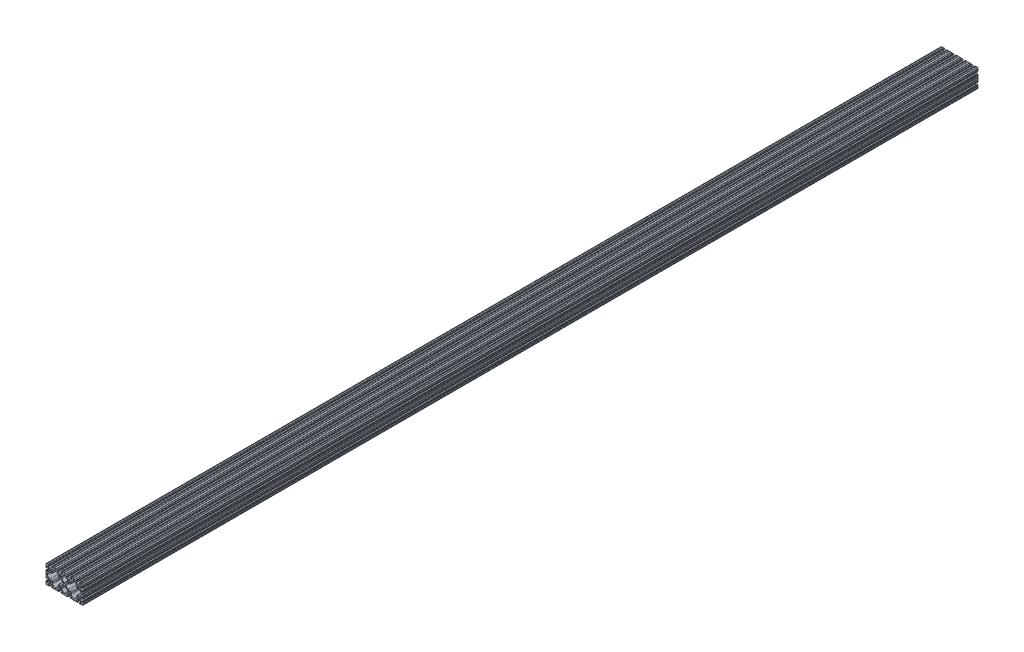
SolidWorks part; units mm, degrees
material "6105-T5 Aluminum"
ref_plane "Front Plane" through (0, 0, 0) normal (0, 0, 1) x (1, 0, 0)
ref_plane "Top Plane" through (0, 0, 0) normal (0, 1, 0) x (1, 0, 0)
ref_plane "Right Plane" through (0, 0, 0) normal (1, 0, 0) x (0, 0, -1)
sketch "Sketch1" plane through (0, 0, 0) normal (0, 0, 1) x (1, 0, 0)
  line L0 (-2.0655, -33.1609) -> (-10.9208, -24.3055)
  line L1 (-12.312, -20.9469) -> (-12.312, -17.1531)
  line L2 (-10.9208, -13.7945) -> (-2.0655, -4.9391)
  line L3 (2.0655, -4.9391) -> (10.9208, -13.7945)
  line L4 (12.312, -17.1531) -> (12.312, -20.9469)
  line L5 (10.9208, -24.3055) -> (2.0655, -33.1609)
  line L6 (22.613, -12.312) -> (17.1531, -12.312)
  line L7 (13.7945, -10.9208) -> (4.9391, -2.0655)
  line L8 (4.9391, 2.0655) -> (13.7945, 10.9208)
  line L9 (17.1531, 12.312) -> (22.613, 12.312)
  line L10 (25.788, 15.487) -> (25.788, 20.9469)
  line L11 (27.1792, 24.3055) -> (36.0345, 33.1609)
  line L12 (40.1655, 33.1609) -> (49.0208, 24.3055)
  line L13 (50.412, 20.9469) -> (50.412, 15.487)
  line L14 (53.587, 12.312) -> (59.0469, 12.312)
  line L15 (62.4055, 10.9208) -> (71.2609, 2.0655)
  line L16 (71.2609, -2.0655) -> (62.4055, -10.9208)
  line L17 (59.0469, -12.312) -> (53.587, -12.312)
  line L18 (50.412, -15.487) -> (50.412, -20.9469)
  line L19 (49.0208, -24.3055) -> (40.1655, -33.1609)
  line L20 (36.0345, -33.1609) -> (27.1792, -24.3055)
  line L21 (25.788, -20.9469) -> (25.788, -15.487)
  line L22 (2.0655, 33.1609) -> (10.9208, 24.3055)
  line L23 (12.312, 20.9469) -> (12.312, 17.1531)
  line L24 (10.9208, 13.7945) -> (2.0655, 4.9391)
  line L25 (-2.0655, 4.9391) -> (-10.9208, 13.7945)
  line L26 (-12.312, 17.1531) -> (-12.312, 20.9469)
  line L27 (-10.9208, 24.3055) -> (-2.0655, 33.1609)
  line L28 (-53.587, -12.312) -> (-59.0469, -12.312)
  line L29 (-62.4055, -10.9208) -> (-71.2609, -2.0655)
  line L30 (-71.2609, 2.0655) -> (-62.4055, 10.9208)
  line L31 (-59.0469, 12.312) -> (-53.587, 12.312)
  line L32 (-50.412, 15.487) -> (-50.412, 20.9469)
  line L33 (-49.0208, 24.3055) -> (-40.1655, 33.1609)
  line L34 (-36.0345, 33.1609) -> (-27.1792, 24.3055)
  line L35 (-25.788, 20.9469) -> (-25.788, 15.487)
  line L36 (-22.613, 12.312) -> (-17.1531, 12.312)
  line L37 (-13.7945, 10.9208) -> (-4.9391, 2.0655)
  line L38 (-4.9391, -2.0655) -> (-13.7945, -10.9208)
  line L39 (-17.1531, -12.312) -> (-22.613, -12.312)
  line L40 (-25.788, -15.487) -> (-25.788, -20.9469)
  line L41 (-27.1792, -24.3055) -> (-36.0345, -33.1609)
  line L42 (-40.1655, -33.1609) -> (-49.0208, -24.3055)
  line L43 (-50.412, -20.9469) -> (-50.412, -15.487)
  line L44 (-3.2004, -38.1) -> (3.2004, -38.1)
  line L45 (4.7244, -38.1) -> (9.5504, -38.1)
  line L46 (11.0744, -38.1) -> (13.4112, -38.1)
  line L47 (14.986, -36.5252) -> (14.986, -35.6108)
  line L48 (13.4112, -34.036) -> (9.652, -34.036)
  line L49 (8.763, -33.147) -> (8.763, -32.5789)
  line L50 (9.0234, -31.9503) -> (13.7945, -27.1792)
  line L51 (17.1531, -25.788) -> (20.9469, -25.788)
  line L52 (24.3055, -27.1792) -> (29.0766, -31.9503)
  line L53 (29.337, -32.5789) -> (29.337, -33.147)
  line L54 (28.448, -34.036) -> (24.6888, -34.036)
  line L55 (23.114, -35.6108) -> (23.114, -36.5252)
  line L56 (24.6888, -38.1) -> (27.0256, -38.1)
  line L57 (28.5496, -38.1) -> (33.3756, -38.1)
  line L58 (34.8996, -38.1) -> (41.3004, -38.1)
  line L59 (42.8244, -38.1) -> (47.6504, -38.1)
  line L60 (49.1744, -38.1) -> (51.5112, -38.1)
  line L61 (53.086, -36.5252) -> (53.086, -35.6108)
  line L62 (51.5112, -34.036) -> (47.752, -34.036)
  line L63 (46.863, -33.147) -> (46.863, -32.5789)
  line L64 (47.1234, -31.9503) -> (51.8945, -27.1792)
  line L65 (55.2531, -25.788) -> (59.0469, -25.788)
  line L66 (62.4055, -27.1792) -> (67.1766, -31.9503)
  line L67 (67.437, -32.5789) -> (67.437, -33.147)
  line L68 (66.548, -34.036) -> (62.7888, -34.036)
  line L69 (61.214, -35.6108) -> (61.214, -36.5252)
  line L70 (62.7888, -38.1) -> (65.1256, -38.1)
  line L71 (66.6496, -38.1) -> (71.4756, -38.1)
  line L72 (72.9996, -38.1) -> (73.025, -38.1)
  line L73 (76.2, -34.925) -> (76.2, -34.8996)
  line L74 (76.2, -33.3756) -> (76.2, -28.5496)
  line L75 (76.2, -27.0256) -> (76.2, -24.6888)
  line L76 (74.6252, -23.114) -> (73.7108, -23.114)
  line L77 (72.136, -24.6888) -> (72.136, -28.448)
  line L78 (71.247, -29.337) -> (70.6789, -29.337)
  line L79 (70.0503, -29.0766) -> (65.2792, -24.3055)
  line L80 (63.888, -20.9469) -> (63.888, -17.1531)
  line L81 (65.2792, -13.7945) -> (70.0503, -9.0234)
  line L82 (70.6789, -8.763) -> (71.247, -8.763)
  line L83 (72.136, -9.652) -> (72.136, -13.4112)
  line L84 (73.7108, -14.986) -> (74.6252, -14.986)
  line L85 (76.2, -13.4112) -> (76.2, -11.0744)
  line L86 (76.2, -9.5504) -> (76.2, -4.7244)
  line L87 (76.2, -3.2004) -> (76.2, 3.2004)
  line L88 (76.2, 4.7244) -> (76.2, 9.5504)
  line L89 (76.2, 11.0744) -> (76.2, 13.4112)
  line L90 (74.6252, 14.986) -> (73.7108, 14.986)
  line L91 (72.136, 13.4112) -> (72.136, 9.652)
  line L92 (71.247, 8.763) -> (70.6789, 8.763)
  line L93 (70.0503, 9.0234) -> (65.2792, 13.7945)
  line L94 (63.888, 17.1531) -> (63.888, 20.9469)
  line L95 (65.2792, 24.3055) -> (70.0503, 29.0766)
  line L96 (70.6789, 29.337) -> (71.247, 29.337)
  line L97 (72.136, 28.448) -> (72.136, 24.6888)
  line L98 (73.7108, 23.114) -> (74.6252, 23.114)
  line L99 (76.2, 24.6888) -> (76.2, 27.0256)
  line L100 (76.2, 28.5496) -> (76.2, 33.3756)
  line L101 (76.2, 34.8996) -> (76.2, 34.925)
  line L102 (73.025, 38.1) -> (72.9996, 38.1)
  line L103 (71.4756, 38.1) -> (66.6496, 38.1)
  line L104 (65.1256, 38.1) -> (62.7888, 38.1)
  line L105 (61.214, 36.5252) -> (61.214, 35.6108)
  line L106 (62.7888, 34.036) -> (66.548, 34.036)
  line L107 (67.437, 33.147) -> (67.437, 32.5789)
  line L108 (67.1766, 31.9503) -> (62.4055, 27.1792)
  line L109 (59.0469, 25.788) -> (55.2531, 25.788)
  line L110 (51.8945, 27.1792) -> (47.1234, 31.9503)
  line L111 (46.863, 32.5789) -> (46.863, 33.147)
  line L112 (47.752, 34.036) -> (51.5112, 34.036)
  line L113 (53.086, 35.6108) -> (53.086, 36.5252)
  line L114 (51.5112, 38.1) -> (49.1744, 38.1)
  line L115 (47.6504, 38.1) -> (42.8244, 38.1)
  line L116 (41.3004, 38.1) -> (34.8996, 38.1)
  line L117 (33.3756, 38.1) -> (28.5496, 38.1)
  line L118 (27.0256, 38.1) -> (24.6888, 38.1)
  line L119 (23.114, 36.5252) -> (23.114, 35.6108)
  line L120 (24.6888, 34.036) -> (28.448, 34.036)
  line L121 (29.337, 33.147) -> (29.337, 32.5789)
  line L122 (29.0766, 31.9503) -> (24.3055, 27.1792)
  line L123 (20.9469, 25.788) -> (17.1531, 25.788)
  line L124 (13.7945, 27.1792) -> (9.0234, 31.9503)
  line L125 (8.763, 32.5789) -> (8.763, 33.147)
  line L126 (9.652, 34.036) -> (13.4112, 34.036)
  line L127 (14.986, 35.6108) -> (14.986, 36.5252)
  line L128 (13.4112, 38.1) -> (11.0744, 38.1)
  line L129 (9.5504, 38.1) -> (4.7244, 38.1)
  line L130 (3.2004, 38.1) -> (-3.2004, 38.1)
  line L131 (-4.7244, 38.1) -> (-9.5504, 38.1)
  line L132 (-11.0744, 38.1) -> (-13.4112, 38.1)
  line L133 (-14.986, 36.5252) -> (-14.986, 35.6108)
  line L134 (-13.4112, 34.036) -> (-9.652, 34.036)
  line L135 (-8.763, 33.147) -> (-8.763, 32.5789)
  line L136 (-9.0234, 31.9503) -> (-13.7945, 27.1792)
  line L137 (-17.1531, 25.788) -> (-20.9469, 25.788)
  line L138 (-24.3055, 27.1792) -> (-29.0766, 31.9503)
  line L139 (-29.337, 32.5789) -> (-29.337, 33.147)
  line L140 (-28.448, 34.036) -> (-24.6888, 34.036)
  line L141 (-23.114, 35.6108) -> (-23.114, 36.5252)
  line L142 (-24.6888, 38.1) -> (-27.0256, 38.1)
  line L143 (-28.5496, 38.1) -> (-33.3756, 38.1)
  line L144 (-34.8996, 38.1) -> (-41.3004, 38.1)
  line L145 (-42.8244, 38.1) -> (-47.6504, 38.1)
  line L146 (-49.1744, 38.1) -> (-51.5112, 38.1)
  line L147 (-53.086, 36.5252) -> (-53.086, 35.6108)
  line L148 (-51.5112, 34.036) -> (-47.752, 34.036)
  line L149 (-46.863, 33.147) -> (-46.863, 32.5789)
  line L150 (-47.1234, 31.9503) -> (-51.8945, 27.1792)
  line L151 (-55.2531, 25.788) -> (-59.0469, 25.788)
  line L152 (-62.4055, 27.1792) -> (-67.1766, 31.9503)
  line L153 (-67.437, 32.5789) -> (-67.437, 33.147)
  line L154 (-66.548, 34.036) -> (-62.7888, 34.036)
  line L155 (-61.214, 35.6108) -> (-61.214, 36.5252)
  line L156 (-62.7888, 38.1) -> (-65.1256, 38.1)
  line L157 (-66.6496, 38.1) -> (-71.4756, 38.1)
  line L158 (-72.9996, 38.1) -> (-73.025, 38.1)
  line L159 (-76.2, 34.925) -> (-76.2, 34.8996)
  line L160 (-76.2, 33.3756) -> (-76.2, 28.5496)
  line L161 (-76.2, 27.0256) -> (-76.2, 24.6888)
  line L162 (-74.6252, 23.114) -> (-73.7108, 23.114)
  line L163 (-72.136, 24.6888) -> (-72.136, 28.448)
  line L164 (-71.247, 29.337) -> (-70.6789, 29.337)
  line L165 (-70.0503, 29.0766) -> (-65.2792, 24.3055)
  line L166 (-63.888, 20.9469) -> (-63.888, 17.1531)
  line L167 (-65.2792, 13.7945) -> (-70.0503, 9.0234)
  line L168 (-70.6789, 8.763) -> (-71.247, 8.763)
  line L169 (-72.136, 9.652) -> (-72.136, 13.4112)
  line L170 (-73.7108, 14.986) -> (-74.6252, 14.986)
  line L171 (-76.2, 13.4112) -> (-76.2, 11.0744)
  line L172 (-76.2, 9.5504) -> (-76.2, 4.7244)
  line L173 (-76.2, 3.2004) -> (-76.2, -3.2004)
  line L174 (-76.2, -4.7244) -> (-76.2, -9.5504)
  line L175 (-76.2, -11.0744) -> (-76.2, -13.4112)
  line L176 (-74.6252, -14.986) -> (-73.7108, -14.986)
  line L177 (-72.136, -13.4112) -> (-72.136, -9.652)
  line L178 (-71.247, -8.763) -> (-70.6789, -8.763)
  line L179 (-70.0503, -9.0234) -> (-65.2792, -13.7945)
  line L180 (-63.888, -17.1531) -> (-63.888, -20.9469)
  line L181 (-65.2792, -24.3055) -> (-70.0503, -29.0766)
  line L182 (-70.6789, -29.337) -> (-71.247, -29.337)
  line L183 (-72.136, -28.448) -> (-72.136, -24.6888)
  line L184 (-73.7108, -23.114) -> (-74.6252, -23.114)
  line L185 (-76.2, -24.6888) -> (-76.2, -27.0256)
  line L186 (-76.2, -28.5496) -> (-76.2, -33.3756)
  line L187 (-76.2, -34.8996) -> (-76.2, -34.925)
  line L188 (-73.025, -38.1) -> (-72.9996, -38.1)
  line L189 (-71.4756, -38.1) -> (-66.6496, -38.1)
  line L190 (-65.1256, -38.1) -> (-62.7888, -38.1)
  line L191 (-61.214, -36.5252) -> (-61.214, -35.6108)
  line L192 (-62.7888, -34.036) -> (-66.548, -34.036)
  line L193 (-67.437, -33.147) -> (-67.437, -32.5789)
  line L194 (-67.1766, -31.9503) -> (-62.4055, -27.1792)
  line L195 (-59.0469, -25.788) -> (-55.2531, -25.788)
  line L196 (-51.8945, -27.1792) -> (-47.1234, -31.9503)
  line L197 (-46.863, -32.5789) -> (-46.863, -33.147)
  line L198 (-47.752, -34.036) -> (-51.5112, -34.036)
  line L199 (-53.086, -35.6108) -> (-53.086, -36.5252)
  line L200 (-51.5112, -38.1) -> (-49.1744, -38.1)
  line L201 (-47.6504, -38.1) -> (-42.8244, -38.1)
  line L202 (-41.3004, -38.1) -> (-34.8996, -38.1)
  line L203 (-33.3756, -38.1) -> (-28.5496, -38.1)
  line L204 (-27.0256, -38.1) -> (-24.6888, -38.1)
  line L205 (-23.114, -36.5252) -> (-23.114, -35.6108)
  line L206 (-24.6888, -34.036) -> (-28.448, -34.036)
  line L207 (-29.337, -33.147) -> (-29.337, -32.5789)
  line L208 (-29.0766, -31.9503) -> (-24.3055, -27.1792)
  line L209 (-20.9469, -25.788) -> (-17.1531, -25.788)
  line L210 (-13.7945, -27.1792) -> (-9.0234, -31.9503)
  line L211 (-8.763, -32.5789) -> (-8.763, -33.147)
  line L212 (-9.652, -34.036) -> (-13.4112, -34.036)
  line L213 (-14.986, -35.6108) -> (-14.986, -36.5252)
  line L214 (-13.4112, -38.1) -> (-11.0744, -38.1)
  line L215 (-9.5504, -38.1) -> (-4.7244, -38.1)
  arc A0 (-2.0655, -33.1609) -> (2.0655, -33.1609) centre (0, -31.0954) ccw
  arc A1 (-12.312, -20.9469) -> (-10.9208, -24.3055) centre (-7.5622, -20.9469) ccw
  arc A2 (-10.9208, -13.7945) -> (-12.312, -17.1531) centre (-7.5622, -17.1531) ccw
  arc A3 (2.0655, -4.9391) -> (-2.0655, -4.9391) centre (0, -7.0046) ccw
  arc A4 (12.312, -17.1531) -> (10.9208, -13.7945) centre (7.5622, -17.1531) ccw
  arc A5 (10.9208, -24.3055) -> (12.312, -20.9469) centre (7.5622, -20.9469) ccw
  arc A6 (25.788, -15.487) -> (22.613, -12.312) centre (22.613, -15.487) ccw
  arc A7 (13.7945, -10.9208) -> (17.1531, -12.312) centre (17.1531, -7.5622) ccw
  arc A8 (4.9391, 2.0655) -> (4.9391, -2.0655) centre (7.0046, 0) ccw
  arc A9 (17.1531, 12.312) -> (13.7945, 10.9208) centre (17.1531, 7.5622) ccw
  arc A10 (22.613, 12.312) -> (25.788, 15.487) centre (22.613, 15.487) ccw
  arc A11 (27.1792, 24.3055) -> (25.788, 20.9469) centre (30.5378, 20.9469) ccw
  arc A12 (40.1655, 33.1609) -> (36.0345, 33.1609) centre (38.1, 31.0954) ccw
  arc A13 (50.412, 20.9469) -> (49.0208, 24.3055) centre (45.6622, 20.9469) ccw
  arc A14 (50.412, 15.487) -> (53.587, 12.312) centre (53.587, 15.487) ccw
  arc A15 (62.4055, 10.9208) -> (59.0469, 12.312) centre (59.0469, 7.5622) ccw
  arc A16 (71.2609, -2.0655) -> (71.2609, 2.0655) centre (69.1954, 0) ccw
  arc A17 (59.0469, -12.312) -> (62.4055, -10.9208) centre (59.0469, -7.5622) ccw
  arc A18 (53.587, -12.312) -> (50.412, -15.487) centre (53.587, -15.487) ccw
  arc A19 (49.0208, -24.3055) -> (50.412, -20.9469) centre (45.6622, -20.9469) ccw
  arc A20 (36.0345, -33.1609) -> (40.1655, -33.1609) centre (38.1, -31.0954) ccw
  arc A21 (25.788, -20.9469) -> (27.1792, -24.3055) centre (30.5378, -20.9469) ccw
  circle A22 centre (-19.05, -19.05) radius 3.3274
  circle A23 centre (-57.15, 19.05) radius 3.3274
  circle A24 centre (57.15, -19.05) radius 3.3274
  circle A25 centre (19.05, 19.05) radius 3.3274
  circle A26 centre (19.05, -19.05) radius 3.3274
  circle A27 centre (57.15, 19.05) radius 3.3274
  circle A28 centre (-57.15, -19.05) radius 3.3274
  circle A29 centre (-19.05, 19.05) radius 3.3274
  arc A30 (2.0655, 33.1609) -> (-2.0655, 33.1609) centre (0, 31.0954) ccw
  arc A31 (12.312, 20.9469) -> (10.9208, 24.3055) centre (7.5622, 20.9469) ccw
  arc A32 (10.9208, 13.7945) -> (12.312, 17.1531) centre (7.5622, 17.1531) ccw
  arc A33 (-2.0655, 4.9391) -> (2.0655, 4.9391) centre (0, 7.0046) ccw
  arc A34 (-12.312, 17.1531) -> (-10.9208, 13.7945) centre (-7.5622, 17.1531) ccw
  arc A35 (-10.9208, 24.3055) -> (-12.312, 20.9469) centre (-7.5622, 20.9469) ccw
  arc A36 (-50.412, -15.487) -> (-53.587, -12.312) centre (-53.587, -15.487) ccw
  arc A37 (-62.4055, -10.9208) -> (-59.0469, -12.312) centre (-59.0469, -7.5622) ccw
  arc A38 (-71.2609, 2.0655) -> (-71.2609, -2.0655) centre (-69.1954, 0) ccw
  arc A39 (-59.0469, 12.312) -> (-62.4055, 10.9208) centre (-59.0469, 7.5622) ccw
  arc A40 (-53.587, 12.312) -> (-50.412, 15.487) centre (-53.587, 15.487) ccw
  arc A41 (-49.0208, 24.3055) -> (-50.412, 20.9469) centre (-45.6622, 20.9469) ccw
  arc A42 (-36.0345, 33.1609) -> (-40.1655, 33.1609) centre (-38.1, 31.0954) ccw
  arc A43 (-25.788, 20.9469) -> (-27.1792, 24.3055) centre (-30.5378, 20.9469) ccw
  arc A44 (-25.788, 15.487) -> (-22.613, 12.312) centre (-22.613, 15.487) ccw
  arc A45 (-13.7945, 10.9208) -> (-17.1531, 12.312) centre (-17.1531, 7.5622) ccw
  arc A46 (-4.9391, -2.0655) -> (-4.9391, 2.0655) centre (-7.0046, 0) ccw
  arc A47 (-17.1531, -12.312) -> (-13.7945, -10.9208) centre (-17.1531, -7.5622) ccw
  arc A48 (-22.613, -12.312) -> (-25.788, -15.487) centre (-22.613, -15.487) ccw
  arc A49 (-27.1792, -24.3055) -> (-25.788, -20.9469) centre (-30.5378, -20.9469) ccw
  arc A50 (-40.1655, -33.1609) -> (-36.0345, -33.1609) centre (-38.1, -31.0954) ccw
  arc A51 (-50.412, -20.9469) -> (-49.0208, -24.3055) centre (-45.6622, -20.9469) ccw
  arc A52 (4.7244, -38.1) -> (3.2004, -38.1) centre (3.9624, -38.1) ccw
  arc A53 (11.0744, -38.1) -> (9.5504, -38.1) centre (10.3124, -38.1) ccw
  arc A54 (13.4112, -38.1) -> (14.986, -36.5252) centre (13.4112, -36.5252) ccw
  arc A55 (14.986, -35.6108) -> (13.4112, -34.036) centre (13.4112, -35.6108) ccw
  arc A56 (8.763, -33.147) -> (9.652, -34.036) centre (9.652, -33.147) ccw
  arc A57 (9.0234, -31.9503) -> (8.763, -32.5789) centre (9.652, -32.5789) ccw
  arc A58 (17.1531, -25.788) -> (13.7945, -27.1792) centre (17.1531, -30.5378) ccw
  arc A59 (24.3055, -27.1792) -> (20.9469, -25.788) centre (20.9469, -30.5378) ccw
  arc A60 (29.337, -32.5789) -> (29.0766, -31.9503) centre (28.448, -32.5789) ccw
  arc A61 (28.448, -34.036) -> (29.337, -33.147) centre (28.448, -33.147) ccw
  arc A62 (24.6888, -34.036) -> (23.114, -35.6108) centre (24.6888, -35.6108) ccw
  arc A63 (23.114, -36.5252) -> (24.6888, -38.1) centre (24.6888, -36.5252) ccw
  arc A64 (28.5496, -38.1) -> (27.0256, -38.1) centre (27.7876, -38.1) ccw
  arc A65 (34.8996, -38.1) -> (33.3756, -38.1) centre (34.1376, -38.1) ccw
  arc A66 (42.8244, -38.1) -> (41.3004, -38.1) centre (42.0624, -38.1) ccw
  arc A67 (49.1744, -38.1) -> (47.6504, -38.1) centre (48.4124, -38.1) ccw
  arc A68 (51.5112, -38.1) -> (53.086, -36.5252) centre (51.5112, -36.5252) ccw
  arc A69 (53.086, -35.6108) -> (51.5112, -34.036) centre (51.5112, -35.6108) ccw
  arc A70 (46.863, -33.147) -> (47.752, -34.036) centre (47.752, -33.147) ccw
  arc A71 (47.1234, -31.9503) -> (46.863, -32.5789) centre (47.752, -32.5789) ccw
  arc A72 (55.2531, -25.788) -> (51.8945, -27.1792) centre (55.2531, -30.5378) ccw
  arc A73 (62.4055, -27.1792) -> (59.0469, -25.788) centre (59.0469, -30.5378) ccw
  arc A74 (67.437, -32.5789) -> (67.1766, -31.9503) centre (66.548, -32.5789) ccw
  arc A75 (66.548, -34.036) -> (67.437, -33.147) centre (66.548, -33.147) ccw
  arc A76 (62.7888, -34.036) -> (61.214, -35.6108) centre (62.7888, -35.6108) ccw
  arc A77 (61.214, -36.5252) -> (62.7888, -38.1) centre (62.7888, -36.5252) ccw
  arc A78 (66.6496, -38.1) -> (65.1256, -38.1) centre (65.8876, -38.1) ccw
  arc A79 (72.9996, -38.1) -> (71.4756, -38.1) centre (72.2376, -38.1) ccw
  arc A80 (73.025, -38.1) -> (76.2, -34.925) centre (73.025, -34.925) ccw
  arc A81 (76.2, -33.3756) -> (76.2, -34.8996) centre (76.2, -34.1376) ccw
  arc A82 (76.2, -27.0256) -> (76.2, -28.5496) centre (76.2, -27.7876) ccw
  arc A83 (76.2, -24.6888) -> (74.6252, -23.114) centre (74.6252, -24.6888) ccw
  arc A84 (73.7108, -23.114) -> (72.136, -24.6888) centre (73.7108, -24.6888) ccw
  arc A85 (71.247, -29.337) -> (72.136, -28.448) centre (71.247, -28.448) ccw
  arc A86 (70.0503, -29.0766) -> (70.6789, -29.337) centre (70.6789, -28.448) ccw
  arc A87 (63.888, -20.9469) -> (65.2792, -24.3055) centre (68.6378, -20.9469) ccw
  arc A88 (65.2792, -13.7945) -> (63.888, -17.1531) centre (68.6378, -17.1531) ccw
  arc A89 (70.6789, -8.763) -> (70.0503, -9.0234) centre (70.6789, -9.652) ccw
  arc A90 (72.136, -9.652) -> (71.247, -8.763) centre (71.247, -9.652) ccw
  arc A91 (72.136, -13.4112) -> (73.7108, -14.986) centre (73.7108, -13.4112) ccw
  arc A92 (74.6252, -14.986) -> (76.2, -13.4112) centre (74.6252, -13.4112) ccw
  arc A93 (76.2, -9.5504) -> (76.2, -11.0744) centre (76.2, -10.3124) ccw
  arc A94 (76.2, -3.2004) -> (76.2, -4.7244) centre (76.2, -3.9624) ccw
  arc A95 (76.2, 4.7244) -> (76.2, 3.2004) centre (76.2, 3.9624) ccw
  arc A96 (76.2, 11.0744) -> (76.2, 9.5504) centre (76.2, 10.3124) ccw
  arc A97 (76.2, 13.4112) -> (74.6252, 14.986) centre (74.6252, 13.4112) ccw
  arc A98 (73.7108, 14.986) -> (72.136, 13.4112) centre (73.7108, 13.4112) ccw
  arc A99 (71.247, 8.763) -> (72.136, 9.652) centre (71.247, 9.652) ccw
  arc A100 (70.0503, 9.0234) -> (70.6789, 8.763) centre (70.6789, 9.652) ccw
  arc A101 (63.888, 17.1531) -> (65.2792, 13.7945) centre (68.6378, 17.1531) ccw
  arc A102 (65.2792, 24.3055) -> (63.888, 20.9469) centre (68.6378, 20.9469) ccw
  arc A103 (70.6789, 29.337) -> (70.0503, 29.0766) centre (70.6789, 28.448) ccw
  arc A104 (72.136, 28.448) -> (71.247, 29.337) centre (71.247, 28.448) ccw
  arc A105 (72.136, 24.6888) -> (73.7108, 23.114) centre (73.7108, 24.6888) ccw
  arc A106 (74.6252, 23.114) -> (76.2, 24.6888) centre (74.6252, 24.6888) ccw
  arc A107 (76.2, 28.5496) -> (76.2, 27.0256) centre (76.2, 27.7876) ccw
  arc A108 (76.2, 34.8996) -> (76.2, 33.3756) centre (76.2, 34.1376) ccw
  arc A109 (76.2, 34.925) -> (73.025, 38.1) centre (73.025, 34.925) ccw
  arc A110 (71.4756, 38.1) -> (72.9996, 38.1) centre (72.2376, 38.1) ccw
  arc A111 (65.1256, 38.1) -> (66.6496, 38.1) centre (65.8876, 38.1) ccw
  arc A112 (62.7888, 38.1) -> (61.214, 36.5252) centre (62.7888, 36.5252) ccw
  arc A113 (61.214, 35.6108) -> (62.7888, 34.036) centre (62.7888, 35.6108) ccw
  arc A114 (67.437, 33.147) -> (66.548, 34.036) centre (66.548, 33.147) ccw
  arc A115 (67.1766, 31.9503) -> (67.437, 32.5789) centre (66.548, 32.5789) ccw
  arc A116 (59.0469, 25.788) -> (62.4055, 27.1792) centre (59.0469, 30.5378) ccw
  arc A117 (51.8945, 27.1792) -> (55.2531, 25.788) centre (55.2531, 30.5378) ccw
  arc A118 (46.863, 32.5789) -> (47.1234, 31.9503) centre (47.752, 32.5789) ccw
  arc A119 (47.752, 34.036) -> (46.863, 33.147) centre (47.752, 33.147) ccw
  arc A120 (51.5112, 34.036) -> (53.086, 35.6108) centre (51.5112, 35.6108) ccw
  arc A121 (53.086, 36.5252) -> (51.5112, 38.1) centre (51.5112, 36.5252) ccw
  arc A122 (47.6504, 38.1) -> (49.1744, 38.1) centre (48.4124, 38.1) ccw
  arc A123 (41.3004, 38.1) -> (42.8244, 38.1) centre (42.0624, 38.1) ccw
  arc A124 (33.3756, 38.1) -> (34.8996, 38.1) centre (34.1376, 38.1) ccw
  arc A125 (27.0256, 38.1) -> (28.5496, 38.1) centre (27.7876, 38.1) ccw
  arc A126 (24.6888, 38.1) -> (23.114, 36.5252) centre (24.6888, 36.5252) ccw
  arc A127 (23.114, 35.6108) -> (24.6888, 34.036) centre (24.6888, 35.6108) ccw
  arc A128 (29.337, 33.147) -> (28.448, 34.036) centre (28.448, 33.147) ccw
  arc A129 (29.0766, 31.9503) -> (29.337, 32.5789) centre (28.448, 32.5789) ccw
  arc A130 (20.9469, 25.788) -> (24.3055, 27.1792) centre (20.9469, 30.5378) ccw
  arc A131 (13.7945, 27.1792) -> (17.1531, 25.788) centre (17.1531, 30.5378) ccw
  arc A132 (8.763, 32.5789) -> (9.0234, 31.9503) centre (9.652, 32.5789) ccw
  arc A133 (9.652, 34.036) -> (8.763, 33.147) centre (9.652, 33.147) ccw
  arc A134 (13.4112, 34.036) -> (14.986, 35.6108) centre (13.4112, 35.6108) ccw
  arc A135 (14.986, 36.5252) -> (13.4112, 38.1) centre (13.4112, 36.5252) ccw
  arc A136 (9.5504, 38.1) -> (11.0744, 38.1) centre (10.3124, 38.1) ccw
  arc A137 (3.2004, 38.1) -> (4.7244, 38.1) centre (3.9624, 38.1) ccw
  arc A138 (-4.7244, 38.1) -> (-3.2004, 38.1) centre (-3.9624, 38.1) ccw
  arc A139 (-11.0744, 38.1) -> (-9.5504, 38.1) centre (-10.3124, 38.1) ccw
  arc A140 (-13.4112, 38.1) -> (-14.986, 36.5252) centre (-13.4112, 36.5252) ccw
  arc A141 (-14.986, 35.6108) -> (-13.4112, 34.036) centre (-13.4112, 35.6108) ccw
  arc A142 (-8.763, 33.147) -> (-9.652, 34.036) centre (-9.652, 33.147) ccw
  arc A143 (-9.0234, 31.9503) -> (-8.763, 32.5789) centre (-9.652, 32.5789) ccw
  arc A144 (-17.1531, 25.788) -> (-13.7945, 27.1792) centre (-17.1531, 30.5378) ccw
  arc A145 (-24.3055, 27.1792) -> (-20.9469, 25.788) centre (-20.9469, 30.5378) ccw
  arc A146 (-29.337, 32.5789) -> (-29.0766, 31.9503) centre (-28.448, 32.5789) ccw
  arc A147 (-28.448, 34.036) -> (-29.337, 33.147) centre (-28.448, 33.147) ccw
  arc A148 (-24.6888, 34.036) -> (-23.114, 35.6108) centre (-24.6888, 35.6108) ccw
  arc A149 (-23.114, 36.5252) -> (-24.6888, 38.1) centre (-24.6888, 36.5252) ccw
  arc A150 (-28.5496, 38.1) -> (-27.0256, 38.1) centre (-27.7876, 38.1) ccw
  arc A151 (-34.8996, 38.1) -> (-33.3756, 38.1) centre (-34.1376, 38.1) ccw
  arc A152 (-42.8244, 38.1) -> (-41.3004, 38.1) centre (-42.0624, 38.1) ccw
  arc A153 (-49.1744, 38.1) -> (-47.6504, 38.1) centre (-48.4124, 38.1) ccw
  arc A154 (-51.5112, 38.1) -> (-53.086, 36.5252) centre (-51.5112, 36.5252) ccw
  arc A155 (-53.086, 35.6108) -> (-51.5112, 34.036) centre (-51.5112, 35.6108) ccw
  arc A156 (-46.863, 33.147) -> (-47.752, 34.036) centre (-47.752, 33.147) ccw
  arc A157 (-47.1234, 31.9503) -> (-46.863, 32.5789) centre (-47.752, 32.5789) ccw
  arc A158 (-55.2531, 25.788) -> (-51.8945, 27.1792) centre (-55.2531, 30.5378) ccw
  arc A159 (-62.4055, 27.1792) -> (-59.0469, 25.788) centre (-59.0469, 30.5378) ccw
  arc A160 (-67.437, 32.5789) -> (-67.1766, 31.9503) centre (-66.548, 32.5789) ccw
  arc A161 (-66.548, 34.036) -> (-67.437, 33.147) centre (-66.548, 33.147) ccw
  arc A162 (-62.7888, 34.036) -> (-61.214, 35.6108) centre (-62.7888, 35.6108) ccw
  arc A163 (-61.214, 36.5252) -> (-62.7888, 38.1) centre (-62.7888, 36.5252) ccw
  arc A164 (-66.6496, 38.1) -> (-65.1256, 38.1) centre (-65.8876, 38.1) ccw
  arc A165 (-72.9996, 38.1) -> (-71.4756, 38.1) centre (-72.2376, 38.1) ccw
  arc A166 (-73.025, 38.1) -> (-76.2, 34.925) centre (-73.025, 34.925) ccw
  arc A167 (-76.2, 33.3756) -> (-76.2, 34.8996) centre (-76.2, 34.1376) ccw
  arc A168 (-76.2, 27.0256) -> (-76.2, 28.5496) centre (-76.2, 27.7876) ccw
  arc A169 (-76.2, 24.6888) -> (-74.6252, 23.114) centre (-74.6252, 24.6888) ccw
  arc A170 (-73.7108, 23.114) -> (-72.136, 24.6888) centre (-73.7108, 24.6888) ccw
  arc A171 (-71.247, 29.337) -> (-72.136, 28.448) centre (-71.247, 28.448) ccw
  arc A172 (-70.0503, 29.0766) -> (-70.6789, 29.337) centre (-70.6789, 28.448) ccw
  arc A173 (-63.888, 20.9469) -> (-65.2792, 24.3055) centre (-68.6378, 20.9469) ccw
  arc A174 (-65.2792, 13.7945) -> (-63.888, 17.1531) centre (-68.6378, 17.1531) ccw
  arc A175 (-70.6789, 8.763) -> (-70.0503, 9.0234) centre (-70.6789, 9.652) ccw
  arc A176 (-72.136, 9.652) -> (-71.247, 8.763) centre (-71.247, 9.652) ccw
  arc A177 (-72.136, 13.4112) -> (-73.7108, 14.986) centre (-73.7108, 13.4112) ccw
  arc A178 (-74.6252, 14.986) -> (-76.2, 13.4112) centre (-74.6252, 13.4112) ccw
  arc A179 (-76.2, 9.5504) -> (-76.2, 11.0744) centre (-76.2, 10.3124) ccw
  arc A180 (-76.2, 3.2004) -> (-76.2, 4.7244) centre (-76.2, 3.9624) ccw
  arc A181 (-76.2, -4.7244) -> (-76.2, -3.2004) centre (-76.2, -3.9624) ccw
  arc A182 (-76.2, -11.0744) -> (-76.2, -9.5504) centre (-76.2, -10.3124) ccw
  arc A183 (-76.2, -13.4112) -> (-74.6252, -14.986) centre (-74.6252, -13.4112) ccw
  arc A184 (-73.7108, -14.986) -> (-72.136, -13.4112) centre (-73.7108, -13.4112) ccw
  arc A185 (-71.247, -8.763) -> (-72.136, -9.652) centre (-71.247, -9.652) ccw
  arc A186 (-70.0503, -9.0234) -> (-70.6789, -8.763) centre (-70.6789, -9.652) ccw
  arc A187 (-63.888, -17.1531) -> (-65.2792, -13.7945) centre (-68.6378, -17.1531) ccw
  arc A188 (-65.2792, -24.3055) -> (-63.888, -20.9469) centre (-68.6378, -20.9469) ccw
  arc A189 (-70.6789, -29.337) -> (-70.0503, -29.0766) centre (-70.6789, -28.448) ccw
  arc A190 (-72.136, -28.448) -> (-71.247, -29.337) centre (-71.247, -28.448) ccw
  arc A191 (-72.136, -24.6888) -> (-73.7108, -23.114) centre (-73.7108, -24.6888) ccw
  arc A192 (-74.6252, -23.114) -> (-76.2, -24.6888) centre (-74.6252, -24.6888) ccw
  arc A193 (-76.2, -28.5496) -> (-76.2, -27.0256) centre (-76.2, -27.7876) ccw
  arc A194 (-76.2, -34.8996) -> (-76.2, -33.3756) centre (-76.2, -34.1376) ccw
  arc A195 (-76.2, -34.925) -> (-73.025, -38.1) centre (-73.025, -34.925) ccw
  arc A196 (-71.4756, -38.1) -> (-72.9996, -38.1) centre (-72.2376, -38.1) ccw
  arc A197 (-65.1256, -38.1) -> (-66.6496, -38.1) centre (-65.8876, -38.1) ccw
  arc A198 (-62.7888, -38.1) -> (-61.214, -36.5252) centre (-62.7888, -36.5252) ccw
  arc A199 (-61.214, -35.6108) -> (-62.7888, -34.036) centre (-62.7888, -35.6108) ccw
  arc A200 (-67.437, -33.147) -> (-66.548, -34.036) centre (-66.548, -33.147) ccw
  arc A201 (-67.1766, -31.9503) -> (-67.437, -32.5789) centre (-66.548, -32.5789) ccw
  arc A202 (-59.0469, -25.788) -> (-62.4055, -27.1792) centre (-59.0469, -30.5378) ccw
  arc A203 (-51.8945, -27.1792) -> (-55.2531, -25.788) centre (-55.2531, -30.5378) ccw
  arc A204 (-46.863, -32.5789) -> (-47.1234, -31.9503) centre (-47.752, -32.5789) ccw
  arc A205 (-47.752, -34.036) -> (-46.863, -33.147) centre (-47.752, -33.147) ccw
  arc A206 (-51.5112, -34.036) -> (-53.086, -35.6108) centre (-51.5112, -35.6108) ccw
  arc A207 (-53.086, -36.5252) -> (-51.5112, -38.1) centre (-51.5112, -36.5252) ccw
  arc A208 (-47.6504, -38.1) -> (-49.1744, -38.1) centre (-48.4124, -38.1) ccw
  arc A209 (-41.3004, -38.1) -> (-42.8244, -38.1) centre (-42.0624, -38.1) ccw
  arc A210 (-33.3756, -38.1) -> (-34.8996, -38.1) centre (-34.1376, -38.1) ccw
  arc A211 (-27.0256, -38.1) -> (-28.5496, -38.1) centre (-27.7876, -38.1) ccw
  arc A212 (-24.6888, -38.1) -> (-23.114, -36.5252) centre (-24.6888, -36.5252) ccw
  arc A213 (-23.114, -35.6108) -> (-24.6888, -34.036) centre (-24.6888, -35.6108) ccw
  arc A214 (-29.337, -33.147) -> (-28.448, -34.036) centre (-28.448, -33.147) ccw
  arc A215 (-29.0766, -31.9503) -> (-29.337, -32.5789) centre (-28.448, -32.5789) ccw
  arc A216 (-20.9469, -25.788) -> (-24.3055, -27.1792) centre (-20.9469, -30.5378) ccw
  arc A217 (-13.7945, -27.1792) -> (-17.1531, -25.788) centre (-17.1531, -30.5378) ccw
  arc A218 (-8.763, -32.5789) -> (-9.0234, -31.9503) centre (-9.652, -32.5789) ccw
  arc A219 (-9.652, -34.036) -> (-8.763, -33.147) centre (-9.652, -33.147) ccw
  arc A220 (-13.4112, -34.036) -> (-14.986, -35.6108) centre (-13.4112, -35.6108) ccw
  arc A221 (-14.986, -36.5252) -> (-13.4112, -38.1) centre (-13.4112, -36.5252) ccw
  arc A222 (-9.5504, -38.1) -> (-11.0744, -38.1) centre (-10.3124, -38.1) ccw
  arc A223 (-3.2004, -38.1) -> (-4.7244, -38.1) centre (-3.9624, -38.1) ccw
extrude "Extrude1" add sketch "Sketch1" against normal blind 3683
